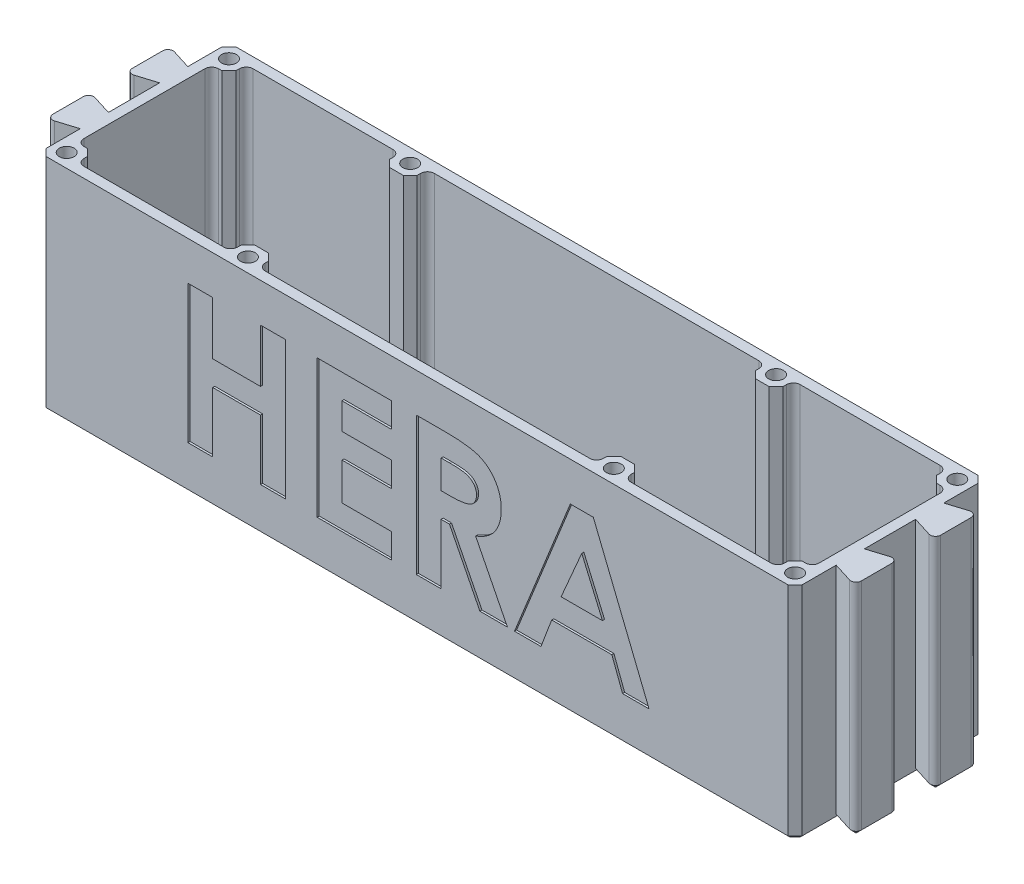
SolidWorks part; units mm, degrees
material "ABS"
ref_plane "Front Plane" through (0, 0, 0) normal (0, 0, 1) x (1, 0, 0)
ref_plane "Top Plane" through (0, 0, 0) normal (0, 1, 0) x (1, 0, 0)
ref_plane "Right Plane" through (0, 0, 0) normal (1, 0, 0) x (0, 0, -1)
sketch "Sketch1" plane through (0, 0, 0) normal (0, 1, 0) x (1, 0, 0)
  line L1 (0, 0) -> (219, 0)
  line L2 (0, 0) -> (0, 55)
  line L3 (0, 55) -> (219, 55)
  line L4 (219, 0) -> (219, 55)
  dimension "D1" = 55
  dimension "D2" = 219
extrude "baseplate" add sketch "Sketch1" along normal blind 4
sketch "Sketch2" plane through (0, 4, 0) normal (0, 1, 0) x (1, 0, 0)
  line L0 (83.3935, 27.5) -> (88.6435, 27.5) construction
  line L1 (83.3935, 49) -> (141.3935, 49) construction
  line L2 (83.3935, 49) -> (83.3935, 6) construction
  line L3 (83.3935, 6) -> (141.3935, 6) construction
  line L4 (141.3935, 49) -> (141.3935, 6) construction
  line L5 (88.6435, 27.5) -> (136.1435, 27.5) construction
  line L6 (136.1435, 27.5) -> (141.3935, 27.5) construction
  line L7 (83.3935, 27.5) -> (0, 27.5) construction
  line L8 (0, 55) -> (0, 0) construction
  line L10 (3, 52) -> (3, 3)
  line L11 (3, 3) -> (216, 3)
  line L12 (216, 3) -> (216, 52)
  line L13 (216, 52) -> (3, 52)
  line L14 (0, 55) -> (0, 0)
  line L15 (0, 0) -> (219, 0)
  line L16 (219, 0) -> (219, 55)
  line L17 (219, 55) -> (0, 55)
  line L18 (0, 55) -> (0, 0)
  line L19 (0, 0) -> (219, 0)
  line L20 (219, 0) -> (219, 55)
  line L21 (219, 55) -> (0, 55)
  circle A0 centre (88.6435, 27.5) radius 2.25 construction
  circle A1 centre (136.1435, 27.5) radius 2.25 construction
  dimension "D3" = 47.5
  dimension "D4" = 4.5
  dimension "D1" = 58
  dimension "D2" = 43
  dimension "D5" = 0
  dimension "D6" = 3
extrude "wall" add sketch "Sketch2" along normal blind 60
chamfer "wall_chamfer" distance 2 angle 45 8 edges at (0, 32, -55) (0, 32, 0) (219, 32, 0) (219, 32, -55) (216, 34, -3) (216, 34, -52) (3, 34, -3) (3, 34, -52)
sketch "Sketch3" plane through (0, 64, 0) normal (0, 1, 0) x (1, 0, 0)
  line L0 (0, 43.081) -> (-5.6527, 44.847)
  line L1 (0, 53) -> (0, 2) construction
  line L2 (-7.6, 43.4153) -> (-7.6, 34.5847)
  line L3 (-5.6527, 33.153) -> (0, 34.919)
  line L4 (0, 34.919) -> (0, 43.081)
  line L5 (109.5, 55) -> (109.5, 3) construction
  line L6 (217, 55) -> (2, 55) construction
  line L7 (5, 3) -> (214, 3) construction
  line L8 (0, 11.919) -> (0, 20.081)
  line L9 (0, 20.081) -> (-5.6527, 21.847)
  line L10 (-7.6, 20.4153) -> (-7.6, 11.5847)
  line L11 (-5.6527, 10.153) -> (0, 11.919)
  line L12 (0, 2) -> (0, 11.919) construction
  line L13 (0, 43.081) -> (0, 53) construction
  line L14 (224.6527, 33.153) -> (219, 34.919)
  line L15 (226.6, 43.4153) -> (226.6, 34.5847)
  line L16 (219, 43.081) -> (224.6527, 44.847)
  line L17 (219, 34.919) -> (219, 43.081)
  line L18 (224.6527, 10.153) -> (219, 11.919)
  line L19 (226.6, 20.4153) -> (226.6, 11.5847)
  line L20 (219, 20.081) -> (224.6527, 21.847)
  line L21 (219, 11.919) -> (219, 20.081)
  arc A0 (-5.6527, 44.847) -> (-7.6, 43.4153) centre (-6.1, 43.4153) ccw
  arc A1 (-5.6527, 33.153) -> (-7.6, 34.5847) centre (-6.1, 34.5847) cw
  arc A2 (-5.6527, 21.847) -> (-7.6, 20.4153) centre (-6.1, 20.4153) ccw
  arc A3 (-5.6527, 10.153) -> (-7.6, 11.5847) centre (-6.1, 11.5847) cw
  arc A4 (224.6527, 33.153) -> (226.6, 34.5847) centre (225.1, 34.5847) ccw
  arc A5 (224.6527, 44.847) -> (226.6, 43.4153) centre (225.1, 43.4153) cw
  arc A6 (224.6527, 10.153) -> (226.6, 11.5847) centre (225.1, 11.5847) ccw
  arc A7 (224.6527, 21.847) -> (226.6, 20.4153) centre (225.1, 20.4153) cw
  dimension "D3" = 1.5
  dimension "D1" = 7.6
  dimension "D2" = 34.7
  dimension "D4" = 2
  dimension "D5" = 23
  dimension "D6" = 8.162
extrude "dovetails" add sketch "Sketch3" against normal up to surface (64 mm away) up to face at (109.5, 0, -27.5)
chamfer "dovetail_chamfers" distance 1.5 angle 45 20 edges at (221.8263, 0, -11.036) (225.9885, 0, -10.3762) (226.6, 0, -16) (225.9885, 0, -21.6238) (221.8263, 0, -20.964) (221.8263, 0, -34.036) (225.9885, 0, -33.3762) (226.6, 0, -39) (225.9885, 0, -44.6238) (221.8263, 0, -43.964) (-2.8263, 0, -43.964) (-6.9885, 0, -44.6238) (-7.6, 0, -39) (-6.9885, 0, -33.3762) (-2.8263, 0, -34.036) (-2.8263, 0, -20.964) (-6.9885, 0, -21.6238) (-7.6, 0, -16) (-6.9885, 0, -10.3762) (-2.8263, 0, -11.036)
chamfer "bottom_chamfer" distance 1 angle 45 12 edges at (219, 0, -27.5) (0, 0, -27.5) (0, 0, -47.2547) (1, 0, -54) (109.5, 0, -55) (218, 0, -54) (219, 0, -47.2547) (0, 0, -7.7453) (1, 0, -1) (109.5, 0, 0) (218, 0, -1) (219, 0, -7.7453)
sketch "Sketch4" plane through (0, 4, 0) normal (0, 1, 0) x (1, 0, 0)
  line L0 (216, 27.5) -> (133.5, 27.5) construction
  line L1 (216, 5) -> (216, 50) construction
  line L2 (133.5, 27.5) -> (85.5, 27.5) construction
  line L3 (85.5, 27.5) -> (3, 27.5) construction
  line L4 (3, 50) -> (3, 5) construction
  line L5 (119.7064, 48.5) -> (119.7064, 27.5) construction
  line L6 (83.5, 48.5) -> (135.5, 48.5)
  line L7 (80.5, 45.5) -> (80.5, 9.5)
  line L8 (83.5, 6.5) -> (135.5, 6.5)
  line L9 (138.5, 45.5) -> (138.5, 9.5)
  line L10 (119.7064, 27.5) -> (119.7064, 6.5) construction
  line L11 (90.5, 35.5) -> (90.5, 19.5)
  line L12 (93.5, 16.5) -> (125.5, 16.5)
  line L13 (128.5, 35.5) -> (128.5, 19.5)
  line L14 (93.5, 38.5) -> (125.5, 38.5)
  line L15 (90.5, 38.5) -> (128.5, 38.5) construction
  line L16 (128.5, 38.5) -> (128.5, 16.5) construction
  line L17 (90.5, 16.5) -> (128.5, 16.5) construction
  line L18 (90.5, 38.5) -> (90.5, 16.5) construction
  circle A0 centre (85.5, 27.5) radius 1.7
  circle A1 centre (133.5, 27.5) radius 1.7
  arc A2 (138.5, 45.5) -> (135.5, 48.5) centre (135.5, 45.5) ccw
  arc A3 (135.5, 6.5) -> (138.5, 9.5) centre (135.5, 9.5) ccw
  arc A4 (83.5, 6.5) -> (80.5, 9.5) centre (83.5, 9.5) cw
  arc A5 (80.5, 45.5) -> (83.5, 48.5) centre (83.5, 45.5) cw
  arc A10 (125.5, 38.5) -> (128.5, 35.5) centre (125.5, 35.5) cw
  arc A11 (128.5, 38.5) -> (128.5, 38.5) centre (128.5, 38.5) ccw construction
  arc A12 (125.5, 16.5) -> (128.5, 19.5) centre (125.5, 19.5) ccw
  arc A13 (128.5, 16.5) -> (128.5, 16.5) centre (128.5, 16.5) ccw construction
  arc A14 (93.5, 16.5) -> (90.5, 19.5) centre (93.5, 19.5) cw
  arc A15 (90.5, 16.5) -> (90.5, 16.5) centre (90.5, 16.5) cw construction
  arc A16 (90.5, 35.5) -> (93.5, 38.5) centre (93.5, 35.5) cw
  arc A17 (90.5, 38.5) -> (90.5, 38.5) centre (90.5, 38.5) cw construction
  point P19 (138.5, 48.5)
  point P22 (138.5, 6.5)
  point P27 (80.5, 48.5)
  dimension "D1" = 48
  dimension "D2" = 3.4
  dimension "D5" = 5
  dimension "D6" = 3
  dimension "D8" = 3
  dimension "D3" = 42
  dimension "D4" = 58
  dimension "D7" = 10
extrude "ssr_mount_plate" add sketch "Sketch4" along normal blind 2
sketch "Sketch5" plane through (0, 4, 0) normal (0, 1, 0) x (1, 0, 0)
  circle A0 centre (133.5, 27.5) radius 1.7 construction
  circle A1 centre (85.5, 27.5) radius 1.7 construction
  circle A2 centre (133.5, 27.5) radius 1.7
  circle A3 centre (85.5, 27.5) radius 1.7
extrude "ssr_mount_holes" cut sketch "Sketch5" against normal through all
sketch "Sketch6" plane through (0, 64, 0) normal (0, 1, 0) x (1, 0, 0)
  line L0 (214, 52) -> (5, 52) construction
  line L1 (80.5, 3) -> (60.5, 3) construction
  line L2 (80.5, 3) -> (80.5, 52) construction
  line L3 (80.5, 52) -> (60.5, 52) construction
  line L4 (60.5, 3) -> (60.5, 52) construction
  line L5 (5, 3) -> (214, 3) construction
  line L6 (80.5, 45.5) -> (80.5, 9.5) construction
  line L7 (217, 55) -> (2, 55) construction
  line L8 (60.5, 52) -> (52.5, 52)
  line L9 (60.5, 52) -> (60.5, 47)
  line L10 (60.5, 47) -> (52.5, 47)
  line L11 (52.5, 52) -> (52.5, 47)
  line L12 (2, 55) -> (8, 55)
  line L13 (0, 53) -> (0, 47)
  line L14 (0, 47) -> (8, 47)
  line L15 (8, 55) -> (8, 47)
  line L16 (0, 53) -> (0, 43.081) construction
  line L17 (2, 55) -> (0, 53) construction
  line L18 (2, 55) -> (0, 53)
  line L19 (3, 27.5) -> (216, 27.5) construction
  line L20 (3, 50) -> (3, 5) construction
  line L21 (216, 5) -> (216, 50) construction
  line L22 (109.5, 52) -> (109.5, 3) construction
  line L23 (214, 52) -> (5, 52) construction
  line L24 (217, 55) -> (219, 53)
  line L25 (219, 53) -> (219, 47)
  line L26 (219, 47) -> (211, 47)
  line L27 (211, 55) -> (211, 47)
  line L28 (217, 55) -> (211, 55)
  line L29 (158.5, 47) -> (166.5, 47)
  line L30 (166.5, 52) -> (166.5, 47)
  line L31 (158.5, 52) -> (166.5, 52)
  line L32 (158.5, 52) -> (158.5, 47)
  line L33 (217, 0) -> (211, 0)
  line L34 (211, 0) -> (211, 8)
  line L35 (219, 8) -> (211, 8)
  line L36 (219, 2) -> (219, 8)
  line L37 (217, 0) -> (219, 2)
  line L38 (158.5, 3) -> (158.5, 8)
  line L39 (158.5, 3) -> (166.5, 3)
  line L40 (166.5, 3) -> (166.5, 8)
  line L41 (158.5, 8) -> (166.5, 8)
  line L42 (60.5, 8) -> (52.5, 8)
  line L43 (52.5, 3) -> (52.5, 8)
  line L44 (60.5, 3) -> (52.5, 3)
  line L45 (60.5, 3) -> (60.5, 8)
  line L46 (2, 0) -> (0, 2)
  line L47 (0, 2) -> (0, 8)
  line L48 (0, 8) -> (8, 8)
  line L49 (8, 0) -> (8, 8)
  line L50 (2, 0) -> (8, 0)
  line L51 (43.6924, 55) -> (43.6924, 52) construction
  dimension "D1" = 20
  dimension "D2" = 5
  dimension "D3" = 8
  dimension "D4" = 8
  dimension "D5" = 3
extrude "lid_mounting_posts" add sketch "Sketch6" against normal up to surface (60 mm away) up to face at (109.5, 4, -27.5)
hole_wizard "lid_mounting_holes" positions "Sketch8" profile "Sketch10" hole size "Ø4.3" standard "DIN"
sketch "Sketch8" plane through (0, 64, 0) normal (0, 1, 0) x (1, 0, 0)
  line L1 (0, 55) -> (8, 55)
  line L2 (0, 55) -> (0, 47)
  line L3 (0, 47) -> (8, 47)
  line L4 (8, 55) -> (8, 47)
  line L5 (0, 55) -> (8, 47) construction
  line L6 (0, 47) -> (8, 55) construction
  line L9 (217, 55) -> (2, 55) construction
  line L12 (52.5, 55) -> (60.5, 55)
  line L13 (52.5, 55) -> (52.5, 47)
  line L14 (52.5, 47) -> (60.5, 47)
  line L15 (60.5, 55) -> (60.5, 47)
  line L16 (52.5, 55) -> (60.5, 47) construction
  line L17 (52.5, 47) -> (60.5, 55) construction
  line L20 (60.5, 47) -> (60.5, 52) construction
  line L21 (52.5, 47) -> (60.5, 47) construction
  line L24 (52.5, 52) -> (52.5, 47) construction
  line L25 (109.5, 55) -> (109.5, 0) construction
  line L26 (2, 0) -> (217, 0) construction
  line L28 (0, 27.5) -> (219, 27.5) construction
  line L29 (0, 34.919) -> (0, 20.081) construction
  line L30 (219, 20.081) -> (219, 34.919) construction
  line L32 (8, 47) -> (8, 52) construction
  line L33 (3, 47) -> (8, 47) construction
  point P1 (4, 51)
  point P48 (56.5, 51)
  point P131 (215, 51)
  point P132 (162.5, 51)
  point P134 (4, 4)
  point P135 (56.5, 4)
  point P136 (162.5, 4)
  point P137 (215, 4)
sketch "Sketch10" plane through (4, 64, -51) normal (1, 0, 0) x (0, 0, 1)
  line L0 (0, 0) -> (0, 11.2919)
  line L1 (0, 11.2919) -> (2.15, 10)
  line L2 (2.15, 10) -> (2.15, 0)
  line L5 (2.15, 0) -> (0, 0)
  line L10 (0, 11.2919) -> (-2.15, 10) construction
  line L11 (0, -6.35) -> (0, 107.95) construction
  dimension "Hole Dia." = 4.3
  dimension "Hole Depth" = 10
  dimension "Drill Angle" = 118
chamfer "posts_chamfers" distance 2 angle 45 12 edges at (52.5, 34, -8) (158.5, 34, -8) (211, 34, -8) (166.5, 34, -8) (60.5, 34, -8) (8, 34, -8) (211, 34, -47) (166.5, 34, -47) (158.5, 34, -47) (60.5, 34, -47) (52.5, 34, -47) (8, 34, -47)
fillet "posts_filets" radius 2 16 edges at (216, 34, -47) (166.5, 34, -3) (166.5, 34, -52) (216, 34, -8) (211, 34, -3) (158.5, 34, -3) (158.5, 34, -52) (211, 34, -52) (60.5, 34, -3) (52.5, 34, -3) (52.5, 34, -52) (8, 34, -3) (3, 34, -8) (60.5, 34, -52) (8, 34, -52) (3, 34, -47)
sketch "Sketch11" plane through (0, 0, 0) normal (0, 0, 1) x (1, 0, 0)
  line L0 (38.5, 12.75) -> (38.5, 32.75) construction
  line L1 (38.5, 32.75) -> (-7.6, 32.75) construction
  line L2 (-7.6, 1.5) -> (-7.6, 64) construction
  line L3 (38.5, 12.75) -> (180.5, 12.75) construction
  line L4 (109.5, 12.75) -> (109.5, 64) construction
  line L5 (2, 64) -> (217, 64) construction
  text T0 "<b>HERA</b>" font "Century Gothic" height 40
  dimension "D1" = 20
  dimension "D2" = 142
extrude "Cut-Extrude2" cut sketch "Sketch11" against normal blind 0.6 and the other way through all
equation "\"D2@Sketch6\"=\"D3@Sketch6\"-\"D5@Sketch6\""
equation "\"D4@Sketch6\"=\"D3@Sketch6\""
